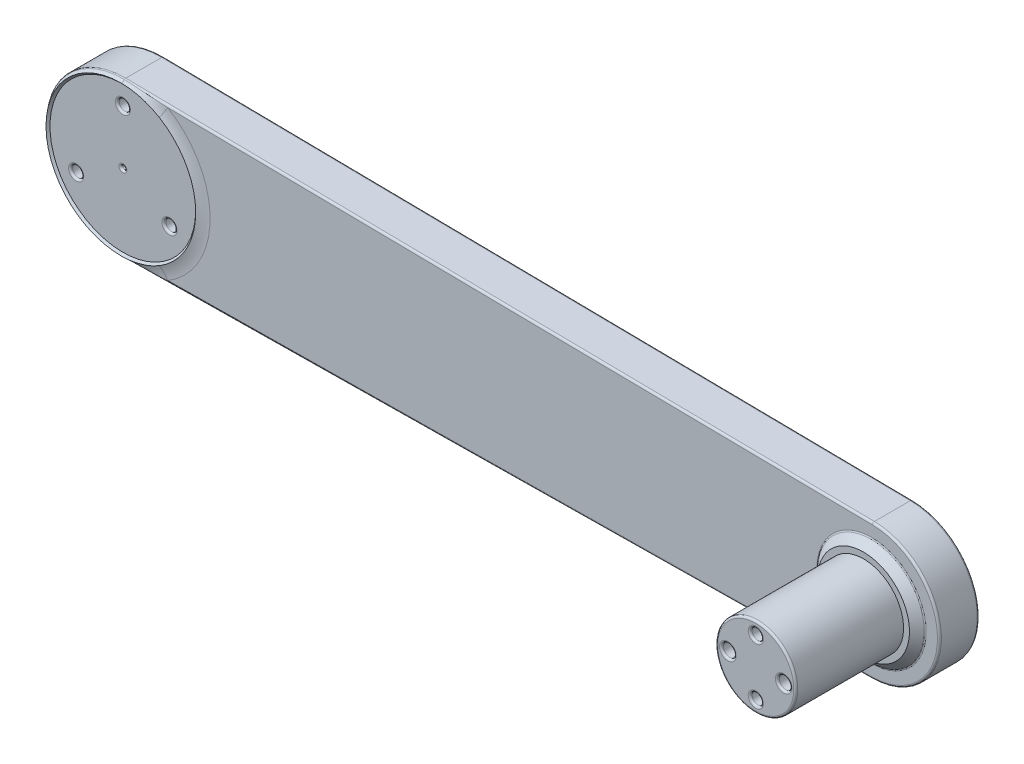
SolidWorks part; units mm, degrees
ref_plane "Front Plane" through (0, 0, 0) normal (0, 0, 1) x (1, 0, 0)
ref_plane "Top Plane" through (0, 0, 0) normal (0, 1, 0) x (1, 0, 0)
ref_plane "Right Plane" through (0, 0, 0) normal (1, 0, 0) x (0, 0, -1)
sketch "Sketch1" plane through (0, 0, 0) normal (0, 0, 1) x (1, 0, 0)
  line L4 (-93.79, 0) -> (93.79, 0) construction
  line L5 (-93.5418, 19.3984) -> (94.0075, 16.9986)
  line L6 (-93.5418, -19.3984) -> (94.0075, -16.9986)
  line L7 (-93.79, 0) -> (-93.79, 13.5) construction
  circle A2 centre (-93.79, 0) radius 0.5
  circle A3 centre (93.79, 0) radius 0.5
  arc A4 (-93.5418, 19.3984) -> (-93.5418, -19.3984) centre (-93.79, 0) ccw
  arc A6 (94.0075, -16.9986) -> (94.0075, 16.9986) centre (93.79, 0) ccw
  circle A7 centre (93.79, 0) radius 12 construction
  circle A8 centre (-93.79, 13.5) radius 1.1 construction
  circle A9 centre (-93.79, 0) radius 13.5 construction
  circle A10 centre (-82.0987, -6.75) radius 1.1 construction
  circle A11 centre (-105.4813, -6.75) radius 1.1 construction
  point P21 (-93.79, 0)
  dimension "D3" = 1
  dimension "D4" = 5
  dimension "D1" = 1
  dimension "D2" = 27
  dimension "D7" = 17
  dimension "D8" = 223.98
  dimension "D9" = 24
  dimension "D11" = 5.9
  dimension "D5" = 187.58
  dimension "D10" = 3
extrude "Boss-Extrude1" add sketch "Sketch1" along normal blind 5 and the other way blind 5
sketch "Sketch8" plane through (0, 0, 5) normal (0, 0, 1) x (1, 0, 0)
  circle A0 centre (-93.79, 0) radius 13.5 construction
  circle A1 centre (-93.79, 13.5) radius 1.4
  circle A2 centre (-82.0987, -6.75) radius 1.4
  circle A3 centre (-105.4813, -6.75) radius 1.4
  point P11 (-93.79, 0)
  dimension "D1" = 2.8
  dimension "D2" = 27
  dimension "D3" = 3
extrude "Cut-Extrude3" cut sketch "Sketch8" against normal through all
sketch "Sketch2" plane through (0, 0, 0) normal (0, 1, 0) x (1, 0, 0)
  line L0 (93.29, -5) -> (94.29, -5) construction
  line L1 (93.29, -5) -> (94.29, -5) construction
  line L2 (93.79, -5) -> (93.79, -34) construction
  line L3 (93.79, -34) -> (103.815, -34)
  line L4 (103.815, -34) -> (103.815, -7)
  line L5 (103.815, -7) -> (105.29, -7)
  line L6 (105.29, -7) -> (107.29, -5)
  line L7 (94.0075, -5) -> (110.79, -5) construction
  line L8 (107.29, -5) -> (93.79, -5)
  line L9 (93.79, -5) -> (93.79, -34)
  line L10 (94.0075, -5) -> (-93.5418, -5) construction
  dimension "D1" = 20.05
  dimension "D2" = 23
  dimension "D3" = 2
  dimension "D4" = 45
  dimension "D5" = 29
revolve "Revolve1" add sketch "Sketch2" angle 360 about L9
sketch "Sketch4" plane through (0, 0, -5) normal (0, 0, -1) x (-1, 0, 0)
  line L0 (-93.79, 0) -> (-93.79, 10.025) construction
  circle A0 centre (-93.79, 7) radius 1.4
  circle A1 centre (-93.79, 7) radius 3 construction
  circle A2 centre (-93.79, 0) radius 10.025 construction
  circle A4 centre (-86.79, 0) radius 1.4
  circle A5 centre (-93.79, -7) radius 1.4
  circle A6 centre (-100.79, 0) radius 1.4
  point P17 (-93.79, 0)
  dimension "D1" = 6
  dimension "D2" = 2.8
  dimension "D3" = 7
  dimension "D4" = 4
extrude "Cut-Extrude1" cut sketch "Sketch4" against normal through all
hole_wizard "CBORE for M5 Hex Head Bolt1" positions "3DSketch1" profile "Sketch5" counterbore size "M5" standard "ANSI Metric" end condition through all
sketch3d "3DSketch1"
  line L1 (100.79, 0, 34) -> (100.79, 0, -5) construction
  line L2 (86.79, 0, 34) -> (86.79, 0, -5) construction
  point P4 (100.79, 0, -5)
  point P8 (86.79, 0, -5)
sketch "Sketch5" plane through (100.79, 0, -5) normal (1, 0, 0) x (0, 1, 0)
  line L0 (0, 0) -> (0, 39)
  line L1 (0, 39) -> (1.6, 39)
  line L3 (1.6, 39) -> (1.6, 3)
  line L4 (1.6, 3) -> (3.5, 3)
  line L5 (3.5, 3) -> (3.5, 0)
  line L7 (3.5, 0) -> (0, 0)
  line L11 (0, -6.35) -> (0, 107.95) construction
  dimension "Thru Hole Dia." = 3.2
  dimension "Thru Hole Depth" = 39
  dimension "C'Bore Dia." = 7
  dimension "C'Bore Depth" = 3
sketch "Sketch6" [suppressed] plane through (0, 0, 0) normal (0, 1, 0) x (1, 0, 0)
  line L0 (-96.825, -5) -> (-95.825, -5) construction
  line L1 (-96.825, -5) -> (-95.825, -5) construction
  line L2 (-96.325, -5) -> (-96.325, -9.6558) construction
  line L3 (-86.3, -5) -> (-86.3, -7)
  line L4 (-96.181, -5) -> (96.4574, -5) construction
  line L5 (-86.3, -7) -> (-84.825, -7)
  line L6 (-84.825, -7) -> (-83.6703, -5)
  line L7 (-83.6703, -5) -> (-86.3, -5)
  dimension "D1" = 23
  dimension "D2" = 20.05
  dimension "D3" = 2
  dimension "D4" = 60
revolve "Revolve2" [suppressed] add sketch "Sketch6" angle 360 about L2
sketch "Sketch7" [suppressed] plane through (0, 0, 5) normal (0, 0, 1) x (1, 0, 0)
  line L0 (-96.325, 7) -> (-96.325, 0) construction
  circle A0 centre (-96.325, 7) radius 1.6
  circle A1 centre (-89.325, 0) radius 1.6
  circle A2 centre (-96.325, -7) radius 1.6
  circle A3 centre (-103.325, 0) radius 1.6
  circle A4 centre (-96.325, 0) radius 10.025 construction
  point P13 (-96.325, 0)
  dimension "D1" = 3.1
  dimension "D2" = 7
  dimension "D3" = 4
extrude "Cut-Extrude2" [suppressed] cut sketch "Sketch7" against normal through all
fillet "Fillet1" radius 0.5 27 edges at (83.765, 0, 34) (85.19, 0, 34) (99.19, 0, 34) (0.2329, -18.1985, 5) (-113.19, 0, 5) (0.2329, 18.1985, 5) (110.79, 0, 5) (-93.29, 0, 5) (-104.0813, -6.75, 5) (-80.6987, -6.75, 5) (-92.39, 13.5, 5) (80.29, 0, 5) (0.2329, 18.1985, -5) (-113.19, 0, -5) (0.2329, -18.1985, -5) (110.79, 0, -5) (-93.29, 0, -5) (94.29, 0, -5) (-104.0813, -6.75, -5) (-80.6987, -6.75, -5) (-92.39, 13.5, -5) (83.29, 0, -5) (97.29, 0, -5) (92.39, -7, 34) (92.39, 7, 34) (92.39, -7, -5) (92.39, 7, -5)
sketch "Sketch9" plane through (0, 0, 0) normal (0, 1, 0) x (1, 0, 0)
  line L0 (-93.29, -4.5) -> (-94.29, -4.5) construction
  line L1 (-93.29, -4.5) -> (-94.29, -4.5) construction
  line L2 (-93.79, -4.5) -> (-93.79, -10.3711) construction
  line L3 (-112.04, -5) -> (-112.54, -5.5)
  line L4 (-112.69, -5) -> (-93.5482, -5) construction
  line L5 (-112.54, -5.5) -> (-112.54, -5)
  line L6 (-107.3813, -5) -> (-103.5813, -5) construction
  line L7 (-112.54, -5) -> (-112.04, -5)
  dimension "D1" = 36.5
  dimension "D2" = 0.5
  dimension "D3" = 45
revolve "Revolve3" add sketch "Sketch9" angle 360 about L2
fillet "Fillet2" radius 10 1 edges at (-75.04, 0, 5)
